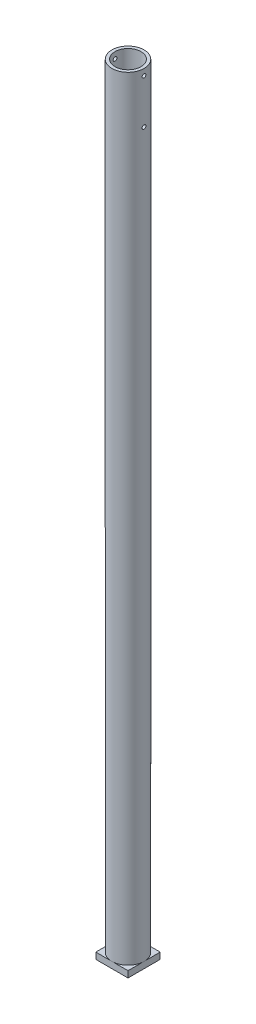
SolidWorks part; units mm, degrees
material "AISI 4130 Steel, annealed at 865C"
ref_plane "Front Plane" through (0, 0, 0) normal (0, 0, 1) x (1, 0, 0)
ref_plane "Top Plane" through (0, 0, 0) normal (0, 1, 0) x (1, 0, 0)
ref_plane "Right Plane" through (0, 0, 0) normal (1, 0, 0) x (0, 0, -1)
sketch "Sketch1" plane through (0, 0, 0) normal (0, 1, 0) x (1, 0, 0)
  circle A0 centre (0, 0) radius 12.7
  circle A1 centre (0, 0) radius 10.287
  dimension "D1" = 25.4
  dimension "D2" = 2.413
  dimension "D3" = 20.574
extrude "Boss-Extrude1" add sketch "Sketch1" along normal blind 609.6
sketch "Sketch2" plane through (0, 0, 0) normal (1, 0, 0) x (0, 0, -1)
  line L0 (0, 609.6) -> (0, 0) construction
  line L1 (12.7, 609.6) -> (-12.7, 609.6) construction
  circle A0 centre (0, 604.6) radius 1.5
  circle A1 centre (0, 569.6) radius 1.5
  dimension "D3" = 3
  dimension "D1" = 5
  dimension "D2" = 35
extrude "Cut-Extrude1" cut sketch "Sketch2" against normal blind 20 and the other way blind 20
sketch "Sketch3" plane through (0, 0, 0) normal (0, 1, 0) x (1, 0, 0)
  line L1 (-12.7, 12.7) -> (12.7, 12.7)
  line L2 (-12.7, 12.7) -> (-12.7, -12.7)
  line L3 (-12.7, -12.7) -> (12.7, -12.7)
  line L4 (12.7, 12.7) -> (12.7, -12.7)
  line L5 (-12.7, 12.7) -> (12.7, -12.7) construction
  line L6 (-12.7, -12.7) -> (12.7, 12.7) construction
  circle A0 centre (0, 0) radius 10.287
  circle A1 centre (0, 0) radius 12.7 construction
  point P0 (0, 0)
  dimension "D3" = 25.4
  dimension "D4" = 2.413
  dimension "D1" = 25.4
  dimension "D2" = 25.4
extrude "Boss-Extrude2" add sketch "Sketch3" against normal blind 5
